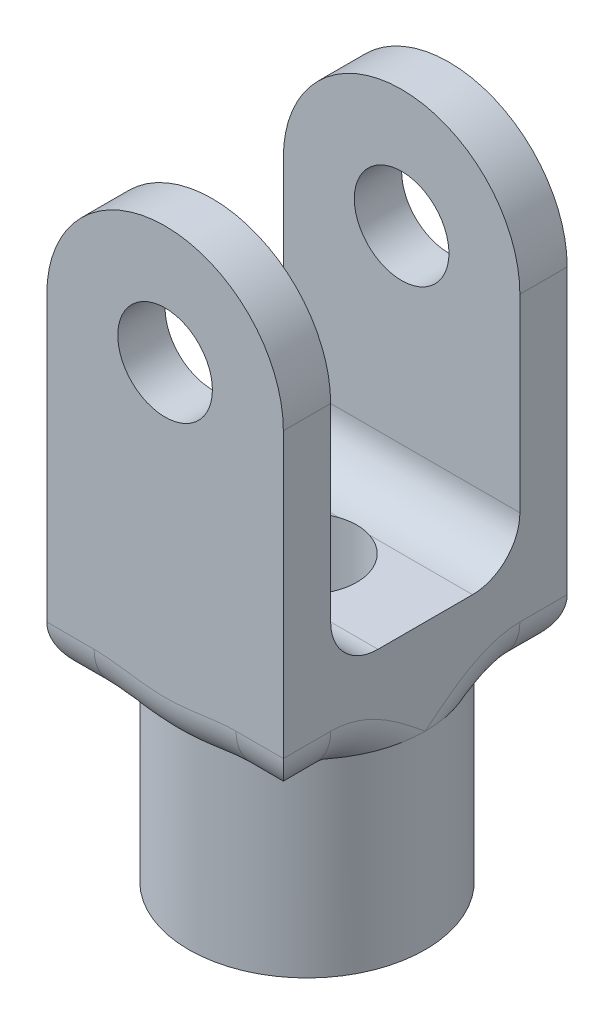
SolidWorks part; units mm, degrees
ref_plane "Front Plane" through (0, 0, 0) normal (0, 0, 1) x (1, 0, 0)
ref_plane "Top Plane" through (0, 0, 0) normal (0, 1, 0) x (1, 0, 0)
ref_plane "Right Plane" through (0, 0, 0) normal (1, 0, 0) x (0, 0, -1)
sketch "Sketch1" plane through (0, 0, 0) normal (0, 1, 0) x (1, 0, 0)
  circle A0 centre (0, 0) radius 5
extrude "Boss-Extrude2" add sketch "Sketch1" along normal blind 8
sketch "Sketch3" plane through (0, 0, 0) normal (0, 0, 1) x (1, 0, 0)
  line L1 (-5, 8) -> (5, 8)
  line L2 (-5, 8) -> (-5, 22)
  line L4 (5, 8) -> (5, 22)
  line L5 (5, 8) -> (-5, 8) construction
  arc A0 (-5, 22) -> (5, 22) centre (0, 22) cw
  circle A1 centre (0, 22) radius 2
  point P6 (0, 8)
extrude "Boss-Extrude3" add sketch "Sketch3" along normal mid plane 12
sketch "Sketch4" plane through (5, 0, 0) normal (1, 0, 0) x (0, 0, -1)
  line L0 (-6, 22) -> (6, 22) construction
  line L1 (4, 12) -> (-4, 12)
  line L2 (4, 12) -> (4, 27.8007)
  line L3 (4, 27.8007) -> (-4, 27.8007)
  line L4 (-4, 12) -> (-4, 27.8007)
  point P6 (0, 12)
  dimension "D1" = 10
  dimension "D2" = 8
extrude "Cut-Extrude1" cut sketch "Sketch4" against normal through all both and the other way through all
fillet "Fillet1" radius 2 2 edges at (0, 12, 4) (0, 12, -4)
hole_wizard "M5 Tapped Hole1" positions "Sketch5" profile "Sketch6" tap size "M5" standard "ISO"
sketch "Sketch5" plane through (0, 0, 0) normal (0, -1, 0) x (-1, 0, 0)
  point P0 (0, 0)
sketch "Sketch6" plane through (0, 0, 0) normal (1, 0, 0) x (0, 0, -1)
  line L0 (0, 0) -> (0, 15.2618)
  line L1 (0, 15.2618) -> (2.1, 14)
  line L2 (2.1, 14) -> (2.1, 0)
  line L5 (2.1, 0) -> (0, 0)
  line L10 (0, 15.2618) -> (-2.1, 14) construction
  line L11 (0, -6.35) -> (0, 107.95) construction
  dimension "Tap Drill Dia." = 4.2
  dimension "Tap Drill Depth" = 14
  dimension "Drill Angle" = 118
cosmetic thread "Hole Thread1" parameters "D1"=10, "D2"=5
fillet "Fillet2" radius 2 6 edges at (-5, 8, -3) (5, 8, 3) (-5, 8, 3) (0, 8, -6) (5, 8, -3) (0, 8, 6)
